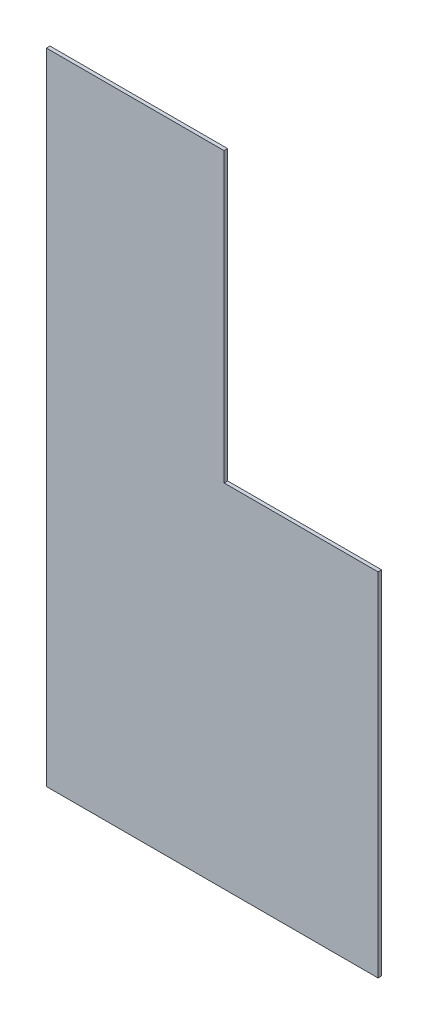
SolidWorks part; units mm, degrees
ref_plane "Plan de face" through (0, 0, 0) normal (0, 0, 1) x (1, 0, 0)
ref_plane "Plan de dessus" through (0, 0, 0) normal (0, 1, 0) x (1, 0, 0)
ref_plane "Plan de droite" through (0, 0, 0) normal (1, 0, 0) x (0, 0, -1)
sketch "Esquisse1" plane through (0, 0, 0) normal (0, 0, 1) x (1, 0, 0)
  line L0 (228.4611, -156.1865) -> (228.4611, -453.1865)
  line L1 (-51.5389, 86.8135) -> (98.4611, 86.8135)
  line L2 (-51.5389, 86.8135) -> (-51.5389, -453.1865)
  line L3 (-51.5389, -453.1865) -> (228.4611, -453.1865)
  line L4 (98.4611, -156.1865) -> (228.4611, -156.1865)
  line L6 (98.4611, 86.8135) -> (98.4611, -156.1865)
  dimension "D2" = 280
  dimension "D3" = 540
  dimension "D4" = 243
  dimension "D1" = 150
extrude "Boss.-Extru.1" add sketch "Esquisse1" along normal blind 3
equation "\"EpaisseurPlaque\"= 3"
equation "\"D1@Boss.-Extru.1\"=\"EpaisseurPlaque\""
equation "\"ProfondeurBoite\"=460"
equation "\"LongueurSyphon\"=170"
equation "\"LargeurSyphon\"=120"
equation "\"HauteurCoteDroit\"= 490"
equation "\"HauteurCoteGauche\"= 540"
equation "\"HauteurSolSyphon\"= 300"
equation "\"HauteurSyphon\"=\"HauteurCoteGauche\"-\"HauteurSolSyphon\""
equation "\"LargeurBoite\"= \"LargeurDroite\" + \"LargeurGauche\" + \"LargeurSyphon\""
equation "\"D3@Esquisse1\"=\"HauteurCoteGauche\""
equation "\"D2@Esquisse1\"=\"LargeurBoite\""
equation "\"D4@Esquisse1\"=\"HauteurSyphon\" +\"EpaisseurPlaque\""
equation "\"LargeurDroite\"=10"
equation "\"LargeurGauche\"=150"
equation "\"D1@Esquisse1\"=\"LargeurGauche\""
